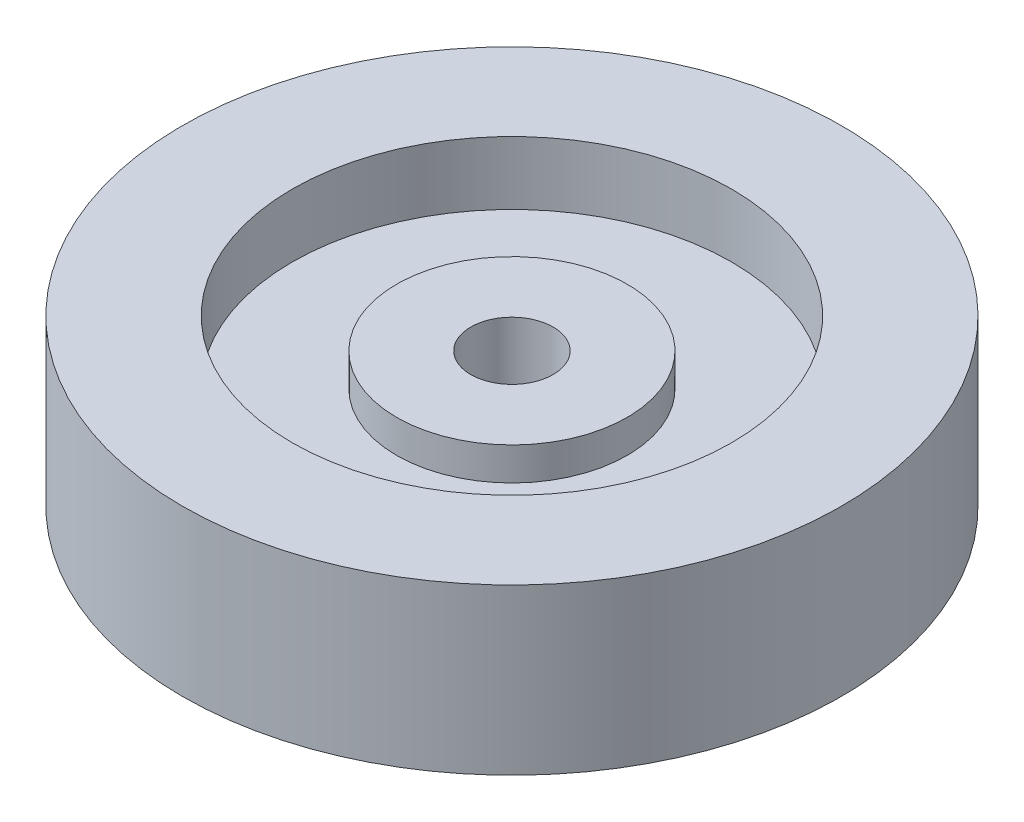
SolidWorks part; units mm, degrees
material "Rubber"
ref_plane "Front Plane" through (0, 0, 0) normal (0, 0, 1) x (1, 0, 0)
ref_plane "Top Plane" through (0, 0, 0) normal (0, 1, 0) x (1, 0, 0)
ref_plane "Right Plane" through (0, 0, 0) normal (1, 0, 0) x (0, 0, -1)
sketch "Sketch2" plane through (0, 0, 0) normal (0, 1, 0) x (1, 0, 0)
  circle A0 centre (0, 0) radius 60
extrude "Boss-Extrude1" add sketch "Sketch2" along normal blind 15 and the other way blind 15
sketch "Sketch3" plane through (0, 15, 0) normal (0, 1, 0) x (1, 0, 0)
  circle A0 centre (0, 0) radius 40
extrude "Cut-Extrude1" cut sketch "Sketch3" against normal blind 11.5
sketch "Sketch4" plane through (0, 3.5, 0) normal (0, 1, 0) x (1, 0, 0)
  circle A0 centre (0, 0) radius 21
extrude "Boss-Extrude2" add sketch "Sketch4" along normal blind 6
sketch "Sketch5" plane through (0, 9.5, 0) normal (0, 1, 0) x (1, 0, 0)
  circle A0 centre (0, 0) radius 7.5
extrude "Cut-Extrude2" cut sketch "Sketch5" against normal blind 20
mirror "Mirror1" about plane through (0, 0, 0) normal (0, 1, 0) of "Boss-Extrude2", "Cut-Extrude1", "Cut-Extrude2"
